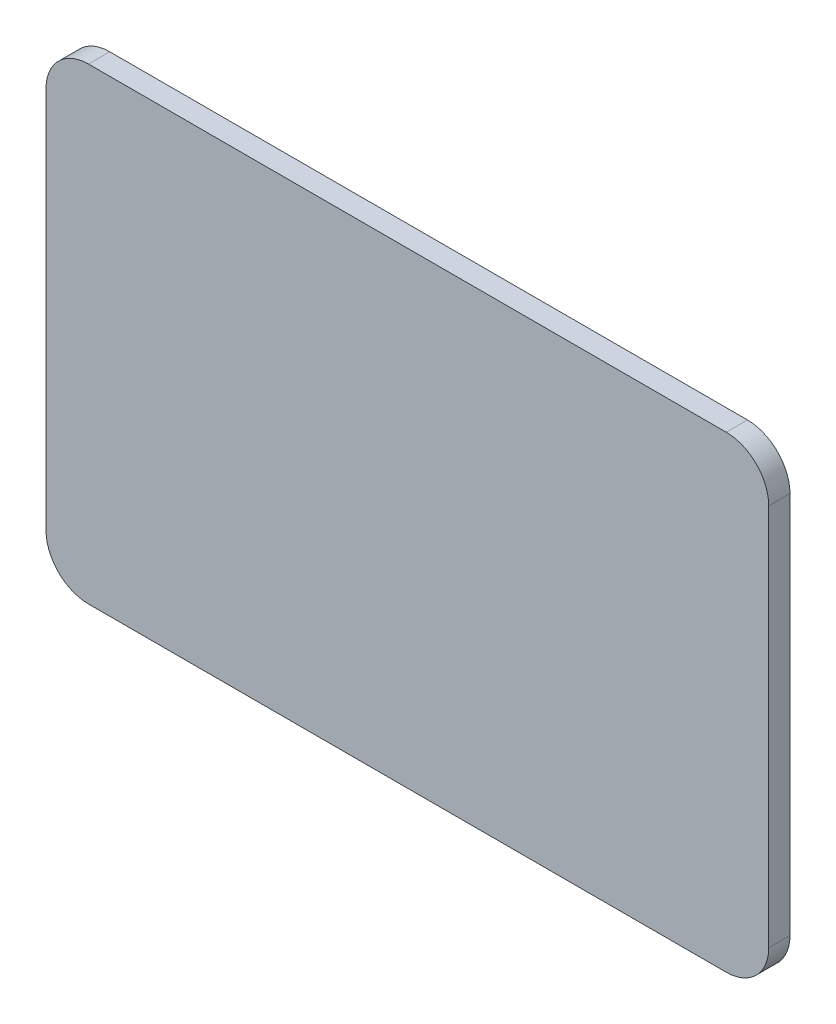
SolidWorks part; units mm, degrees
material "PC High Viscosity"
ref_plane "X-Y Datum" through (0, 0, 0) normal (0, 0, 1) x (1, 0, 0)
ref_plane "X-Z Datum" through (0, 0, 0) normal (0, 1, 0) x (1, 0, 0)
ref_plane "Y-Z Datum" through (0, 0, 0) normal (1, 0, 0) x (0, 0, -1)
sketch "Sketch1" plane through (0, 0, 0) normal (0, 0, 1) x (1, 0, 0)
  line L1 (-53.975, 34.925) -> (53.975, 34.925)
  line L2 (-53.975, 34.925) -> (-53.975, -34.925)
  line L3 (-53.975, -34.925) -> (53.975, -34.925)
  line L4 (53.975, 34.925) -> (53.975, -34.925)
  line L5 (-53.975, 34.925) -> (53.975, -34.925) construction
  line L6 (-53.975, -34.925) -> (53.975, 34.925) construction
  point P0 (0, 0)
  dimension "D1" = 107.95
  dimension "D2" = 69.85
extrude "Boss-Extrude1" add sketch "Sketch1" along normal blind 3.175
fillet "Fillet1" radius 6.35 4 edges at (53.975, -34.925, 1.5875) (53.975, 34.925, 1.5875) (-53.975, 34.925, 1.5875) (-53.975, -34.925, 1.5875)
